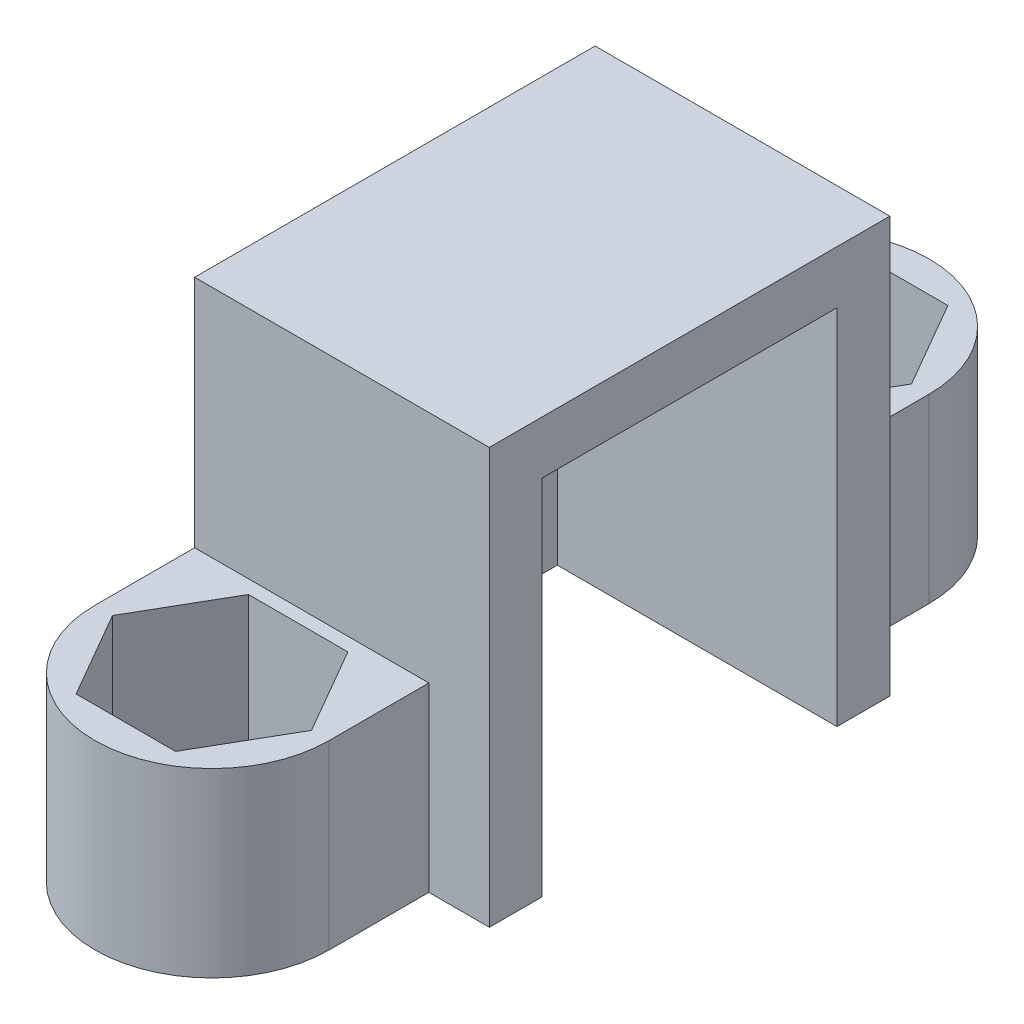
SolidWorks part; units mm, degrees
ref_plane "Přední rovina" through (0, 0, 0) normal (0, 0, 1) x (1, 0, 0)
ref_plane "Horní rovina" through (0, 0, 0) normal (0, 1, 0) x (1, 0, 0)
ref_plane "Pravá rovina" through (0, 0, 0) normal (1, 0, 0) x (0, 0, -1)
sketch "Sketch1" plane through (0, 0, 0) normal (1, 0, 0) x (0, 0, -1)
  line L0 (-4.875, 5.125) -> (-4.875, -6.875)
  line L1 (-6.625, 6.875) -> (6.625, 6.875)
  line L2 (-6.625, 6.875) -> (-6.625, -6.875)
  line L3 (-6.625, -6.875) -> (6.625, -6.875)
  line L4 (6.625, 6.875) -> (6.625, -6.875)
  line L5 (-6.625, 6.875) -> (6.625, -6.875) construction
  line L6 (-6.625, -6.875) -> (6.625, 6.875) construction
  line L7 (-4.875, 5.125) -> (4.875, 5.125)
  line L8 (4.875, 5.125) -> (4.875, -6.875)
  point P0 (0, 0)
  dimension "D1" = 1.75
  dimension "D2" = 1.75
  dimension "D3" = 1.75
  dimension "D4" = 9.75
  dimension "D5" = 12
extrude "Boss-Extrude1" add sketch "Sketch1" along normal blind 9.75 contours L7 L8 L3 L4 L1 L2 L0 region at (0, -0.875, 5.066)
sketch "Sketch2" plane through (0, -6.875, 0) normal (0, -1, 0) x (1, 0, 0)
  line L0 (3.875, 1.9293) -> (3.875, 9.925) construction
  line L1 (0, 1.9293) -> (0, 9.925)
  line L4 (9.75, 4.875) -> (0, 4.875) construction
  line L5 (7.75, 1.9293) -> (7.75, 9.925)
  line L6 (9.75, 6.625) -> (0, 6.625) construction
  line L7 (9.75, 4.875) -> (0, 4.875)
  line L8 (2.2296, 12.775) -> (0.5841, 9.925)
  line L9 (0.5841, 9.925) -> (2.2296, 7.075)
  line L10 (2.2296, 7.075) -> (5.5204, 7.075)
  line L11 (5.5204, 7.075) -> (7.1659, 9.925)
  line L12 (7.1659, 9.925) -> (5.5204, 12.775)
  line L13 (5.5204, 12.775) -> (2.2296, 12.775)
  line L14 (0, 6.625) -> (0, -6.625) construction
  circle A3 centre (3.875, 9.925) radius 2.85 construction
  arc A4 (0, 1.9293) -> (7.75, 1.9293) centre (3.875, 1.9293) ccw
  arc A5 (7.75, 9.925) -> (0, 9.925) centre (3.875, 9.925) ccw
  point P1 (3.875, 5.9271)
  line M9 (9.75, 6.625) -> (0, 6.625)
  dimension "D1" = 5.7
  dimension "D3" = 3.3
  dimension "D2" = 7.75
extrude "Boss-Extrude2" add sketch "Sketch2" against normal blind 5 from offset 1 contours M9 region at (0.1056, -6.875, 8.275) offset against normal yes
sketch "Sketch3" plane through (0, -5.875, 0) normal (0, -1, 0) x (1, 0, 0)
  line L6 (7.75, 6.625) -> (7.75, 9.925) construction
  line L7 (0, 6.625) -> (0, 9.925) construction
  line L8 (7.75, 6.625) -> (7.75, 9.925)
  line L9 (0, 6.625) -> (0, 9.925)
  line L10 (7.75, 6.625) -> (0, 6.625)
  circle A2 centre (3.875, 9.925) radius 1.6
  arc A3 (7.75, 9.925) -> (0, 9.925) centre (3.875, 9.925) ccw construction
  arc A4 (7.75, 9.925) -> (0, 9.925) centre (3.875, 9.925) ccw
  dimension "D1" = 3.2
extrude "Boss-Extrude3" add sketch "Sketch3" along normal up to surface (1 mm away) up to face at (4.875, -6.875, 5.75)
mirror "Mirror1" about plane through (0, 0, 0) normal (0, 0, 1) of "Boss-Extrude3", "Boss-Extrude2"
sketch "Sketch4" plane through (0, 0, 0) normal (-1, 0, 0) x (0, 0, 1)
  line L0 (-6.625, 6.875) -> (-6.625, -6.875)
  line L1 (-4.875, -6.875) -> (-9.925, -6.875) construction
  line L2 (-6.625, -6.875) -> (-4.375, -6.875)
  line L3 (-4.375, -6.875) -> (-4.375, 4.625)
  line L4 (-4.375, 4.625) -> (4.375, 4.625)
  line L5 (4.375, 4.625) -> (4.375, -6.875)
  line L6 (4.375, -6.875) -> (6.625, -6.875)
  line L7 (9.925, -6.875) -> (4.875, -6.875) construction
  line L8 (6.625, -6.875) -> (6.625, 6.875)
  line L9 (6.625, 6.875) -> (-6.625, 6.875)
  line L10 (6.625, 6.875) -> (6.625, -0.875) construction
  line L11 (4.875, 5.125) -> (4.875, -6.875) construction
  line L12 (4.875, 5.125) -> (-4.875, 5.125) construction
  line L13 (-4.875, 5.125) -> (-4.875, -6.875) construction
  dimension "D1" = 0.5
  dimension "D2" = 0.5
  dimension "D3" = 0.5
extrude "Boss-Extrude4" add sketch "Sketch4" against normal blind 0.5
